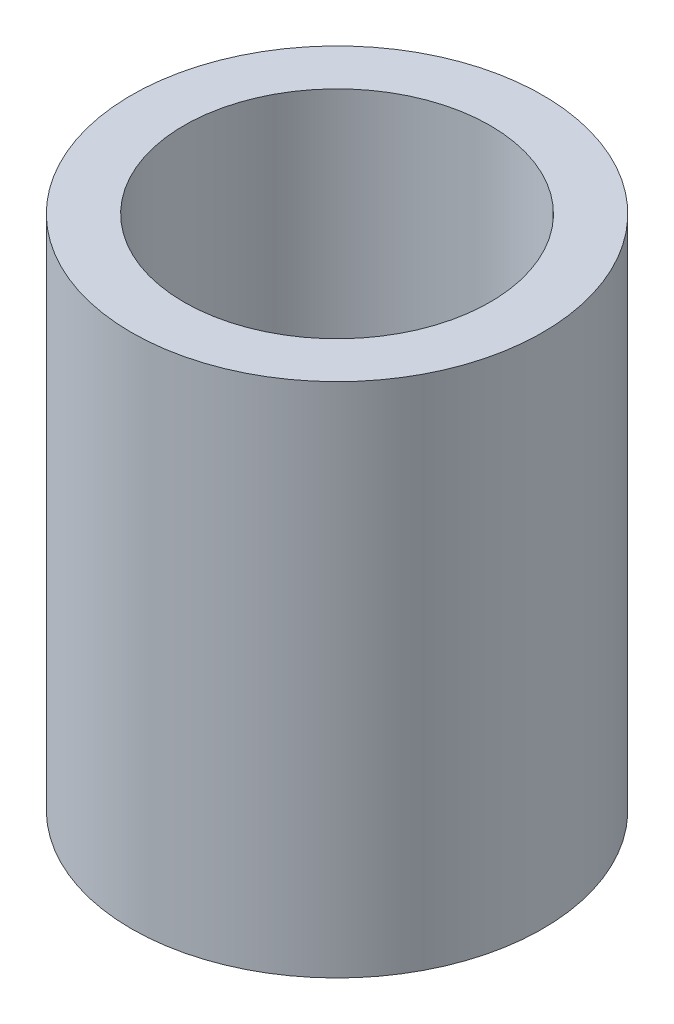
SolidWorks part; units mm, degrees
ref_plane "Front Plane" through (0, 0, 0) normal (0, 0, 1) x (1, 0, 0)
ref_plane "Top Plane" through (0, 0, 0) normal (0, 1, 0) x (1, 0, 0)
ref_plane "Right Plane" through (0, 0, 0) normal (1, 0, 0) x (0, 0, -1)
sketch "Sketch1" plane through (0, 0, 0) normal (0, 1, 0) x (1, 0, 0)
  circle A0 centre (0, 0) radius 30
  dimension "SLEEVE_OD" = 60
extrude "Boss-Extrude1" add sketch "Sketch1" along normal blind 75.3549
sketch "Sketch2" plane through (0, 0, 0) normal (0, 1, 0) x (1, 0, 0)
  circle A0 centre (0, 0) radius 22.3321
  dimension "BORE_D" = 44.6643
extrude "Cut-Extrude1" cut sketch "Sketch2" along normal through all
chamfer "Chamfer1" distance 3.1603 angle 60 rebuild error yes
